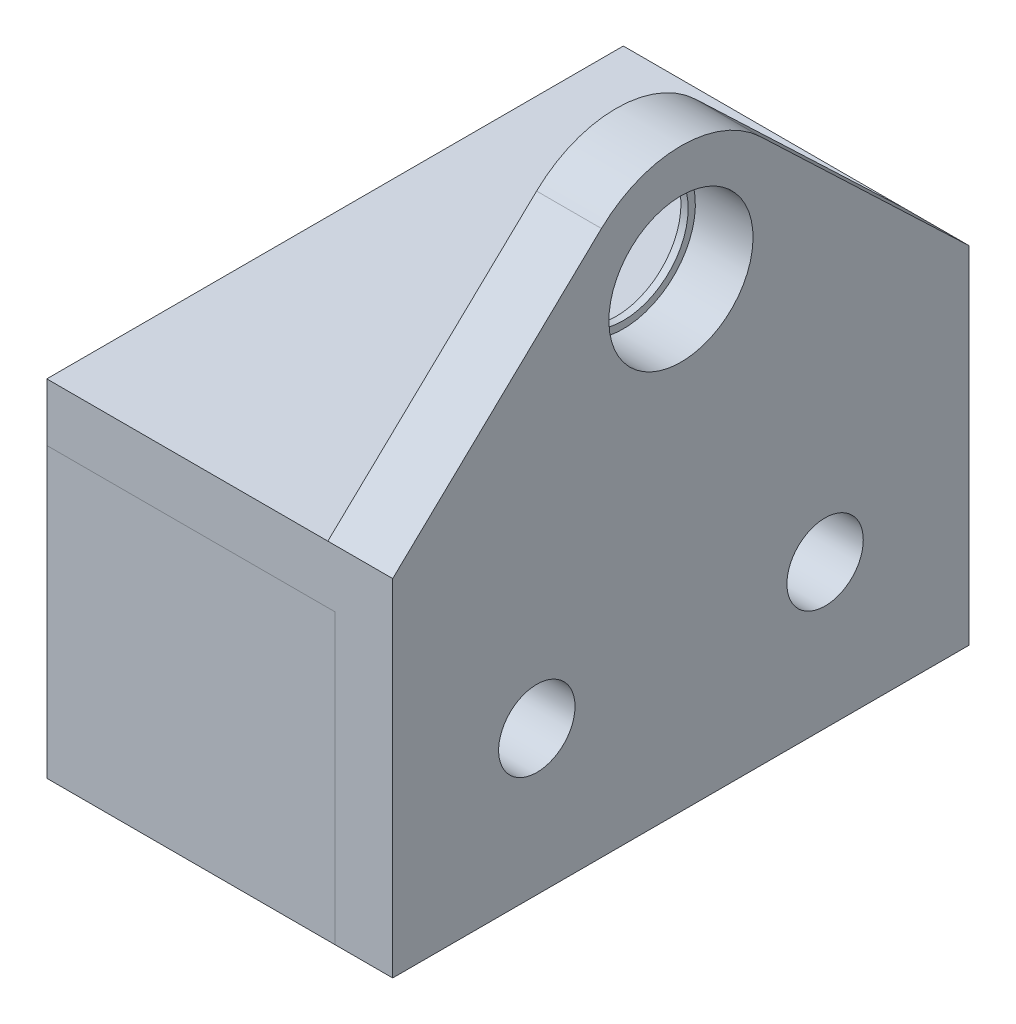
SolidWorks part; units mm, degrees
material "ABS"
ref_plane "Спереди" through (0, 0, 0) normal (0, 0, 1) x (1, 0, 0)
ref_plane "Сверху" through (0, 0, 0) normal (0, 1, 0) x (1, 0, 0)
ref_plane "Справа" through (0, 0, 0) normal (1, 0, 0) x (0, 0, -1)
sketch "Эскиз2" plane through (0, 0, 0) normal (0, 0, 1) x (1, 0, 0)
  line L1 (10, -10) -> (-10, -10)
  line L2 (10, -10) -> (10, 10)
  line L3 (10, 10) -> (-10, 10)
  line L4 (-10, -10) -> (-10, 10)
  line L5 (10, -10) -> (-10, 10) construction
  line L6 (10, 10) -> (-10, -10) construction
  point P0 (0, 0)
  dimension "D1" = 20
  dimension "D2" = 20
extrude "Бобышка-Вытянуть1" add sketch "Эскиз2" along normal mid plane 40
sketch "Эскиз3" plane through (10, 0, 0) normal (1, 0, 0) x (0, 0, -1)
  line L1 (-20, 10) -> (20, 10)
  line L2 (-20, 10) -> (20, 10) construction
  line L3 (-20, 10) -> (-20, 14)
  line L4 (-20, 14) -> (20, 14)
  line L5 (-20, 10) -> (20, 10)
  line L6 (20, 10) -> (20, 14)
  line L7 (20, -10) -> (20, 10)
  line L8 (20, 10) -> (-20, 10)
  line L9 (-20, 10) -> (-20, -10)
  line L10 (-20, -10) -> (20, -10)
  line L11 (20, -10) -> (20, 10)
  line L12 (0, 14) -> (0, 10) construction
  line L13 (-20, 10) -> (-20, -10)
  line L14 (-20, -10) -> (20, -10)
  line L15 (-20, 12) -> (20, 12) construction
  point P3 (0, 0)
  point P224 (0, 12)
  dimension "D1" = 4
  dimension "D3" = 0
extrude "Бобышка-Вытянуть2" add sketch "Эскиз3" along normal blind 4 separate body
hole_wizard "Отверстие с зазором M51" positions "Эскиз4" profile "Эскиз5" hole size "M5" standard "ISO" end condition up to next
sketch "Эскиз4" plane through (14, 0, 0) normal (1, 0, 0) x (0, 0, -1)
  point P0 (-10, 0)
  point P2 (10, 0)
  dimension "D1" = 20
  dimension "D2" = 10
sketch "Эскиз5" plane through (14, 0, 10) normal (0, 1, 0) x (0, 0, -1)
  line L0 (0, 0) -> (0, 24)
  line L1 (0, 24) -> (2.65, 24)
  line L2 (2.65, 24) -> (2.65, 0)
  line L5 (2.65, 0) -> (0, 0)
  line L11 (0, -6.35) -> (0, 107.95) construction
  dimension "Диаметр сквозного отверстия" = 5.3
  dimension "Глубина сквозного отверстия" = 24
sketch "Эскиз6" plane through (10, 0, 0) normal (-1, 0, 0) x (0, 0, 1)
  line L0 (-20, -10) -> (-20, 14) construction
  line L1 (20, 14) -> (-20, 14)
  line L3 (20, 14) -> (20, 10)
  line L5 (20, 10) -> (-20, 10)
  line L6 (-20, 14) -> (-20, 10)
  line L7 (0, 10) -> (0, 14) construction
  line L8 (20, 12) -> (-20, 12) construction
  point P242 (0, 12)
  dimension "D1" = 4
extrude "Бобышка-Вытянуть3" add sketch "Эскиз6" along normal blind 20
sketch "Эскиз7" plane through (0, 10, 0) normal (0, -1, 0) x (1, 0, 0)
  line L0 (0, 0) -> (-50000, 0) construction
  line L1 (-3.05, 8) -> (3.05, 8)
  line L2 (-3.05, 8) -> (-3.05, 16)
  line L3 (-3.05, 16) -> (3.05, 16)
  line L4 (3.05, 8) -> (3.05, 16)
  line L5 (0, 16) -> (0, 8) construction
  line L6 (-3.05, 12) -> (3.05, 12) construction
  line L7 (-3.05, -12) -> (3.05, -12) construction
  line L8 (0, -16) -> (0, -8) construction
  line L9 (3.05, -8) -> (3.05, -16)
  line L10 (-3.05, -16) -> (3.05, -16)
  line L11 (-3.05, -8) -> (-3.05, -16)
  line L12 (-3.05, -8) -> (3.05, -8)
  point P14 (0, -12)
  point P56 (0, 12)
  dimension "D1" = 6.1
  dimension "D2" = 8
  dimension "D3" = 12
extrude "Бобышка-Вытянуть4" add sketch "Эскиз7" along normal blind 3
chamfer "Фаска1" distance 1 angle 45 4 edges at (-3.05, 7, 12) (3.05, 7, 12) (3.05, 7, -12) (-3.05, 7, -12)
sketch "Эскиз8" plane through (14, 0, 0) normal (1, 0, 0) x (0, 0, -1)
  line L0 (-20, 14) -> (-5.5172, 27.7931)
  line L1 (5.5172, 27.7931) -> (20, 14)
  line L2 (-20, 14) -> (20, 14) construction
  circle A0 centre (0, 22) radius 5
  arc A1 (-5.5172, 27.7931) -> (5.5172, 27.7931) centre (0, 22) cw
  point P8 (0, 17.2123)
  line M8 (20, 14) -> (-20, 14)
  dimension "D1" = 10
  dimension "D2" = 3
  dimension "D3" = 3
extrude "Бобышка-Вытянуть5" add sketch "Эскиз8" against normal blind 4.5 contours A1 L0 L1 A0 M8 region at (14, 20.5846, 12.4615)
sketch "Эскиз9" plane through (9.5, 0, 0) normal (-1, 0, 0) x (0, 0, 1)
  circle A0 centre (0, 22) radius 5 construction
  circle A1 centre (0, 22) radius 5
  circle A2 centre (0, 22) radius 4.5
  dimension "D1" = 0.5
extrude "Бобышка-Вытянуть6" add sketch "Эскиз9" against normal offset from surface (0.5 mm away) 4 up to face at (14, 0, 7.35)
